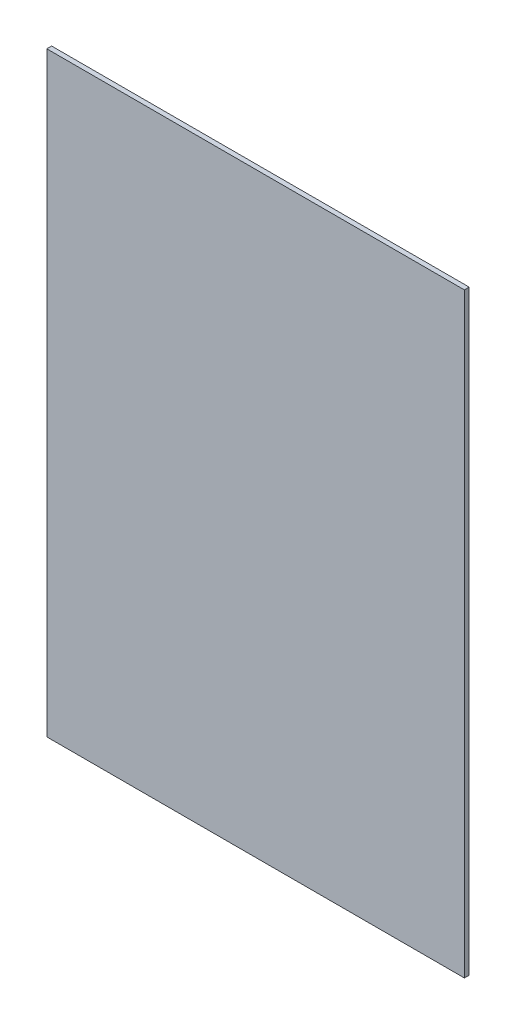
SolidWorks part; units mm, degrees
material "1060 Alloy"
ref_plane "Front Plane" through (0, 0, 0) normal (0, 0, 1) x (1, 0, 0)
ref_plane "Top Plane" through (0, 0, 0) normal (0, 1, 0) x (1, 0, 0)
ref_plane "Right Plane" through (0, 0, 0) normal (1, 0, 0) x (0, 0, -1)
sketch "Sketch1" plane through (0, 0, 0) normal (0, 0, 1) x (1, 0, 0)
  line L1 (-100, 142.695) -> (100, 142.695)
  line L2 (-100, 142.695) -> (-100, -142.695)
  line L3 (-100, -142.695) -> (100, -142.695)
  line L4 (100, 142.695) -> (100, -142.695)
  line L5 (-100, 142.695) -> (100, -142.695) construction
  line L6 (-100, -142.695) -> (100, 142.695) construction
  point P0 (0, 0)
  dimension "D1" = 200
  dimension "D2" = 285.39
extrude "Boss-Extrude1" add sketch "Sketch1" along normal blind 2.305
